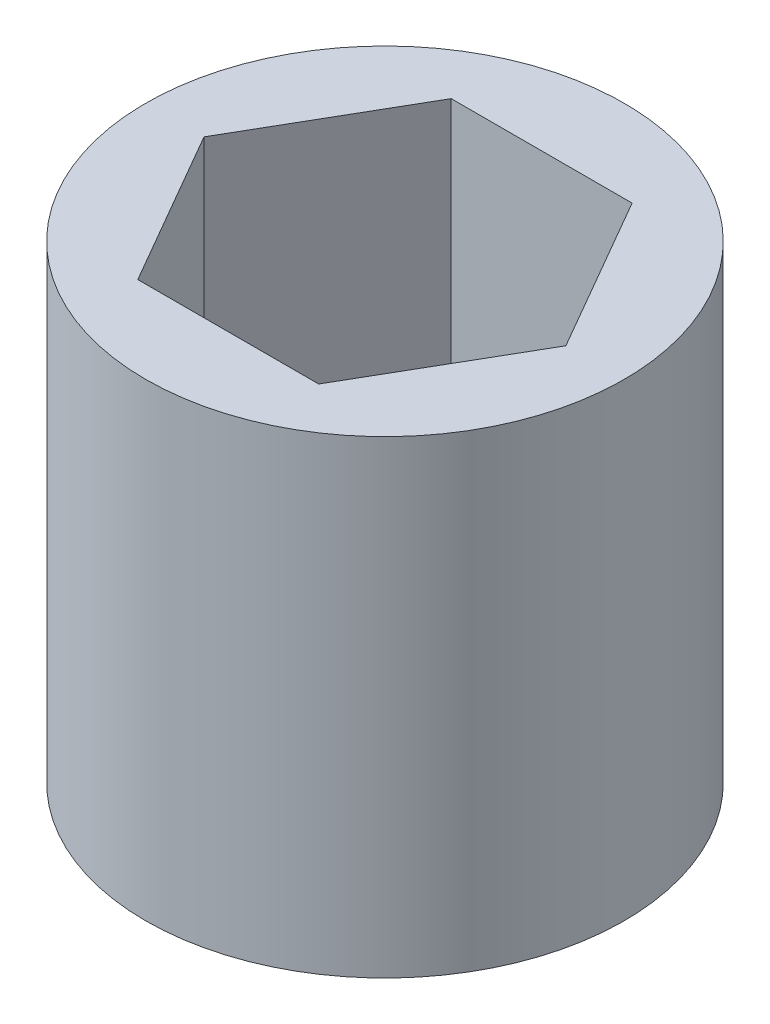
SolidWorks part; units mm, degrees
ref_plane "Front Plane" through (0, 0, 0) normal (0, 0, 1) x (1, 0, 0)
ref_plane "Top Plane" through (0, 0, 0) normal (0, 1, 0) x (1, 0, 0)
ref_plane "Right Plane" through (0, 0, 0) normal (1, 0, 0) x (0, 0, -1)
sketch "Sketch1" plane through (0, 0, 0) normal (0, 1, 0) x (1, 0, 0)
  line L0 (-2.8362, -4.9125) -> (2.8362, -4.9125)
  line L1 (2.8362, -4.9125) -> (5.6725, 0)
  line L2 (5.6725, 0) -> (2.8362, 4.9125)
  line L3 (2.8362, 4.9125) -> (-2.8362, 4.9125)
  line L4 (-2.8362, 4.9125) -> (-5.6725, 0)
  line L5 (-5.6725, 0) -> (-2.8362, -4.9125)
  circle A0 centre (0, 0) radius 7.5
  point P7 (0, 0)
  point P9 (0, 4.9125)
  dimension "D3" = 15
  dimension "D1" = 120
  dimension "D2" = 9.825
extrude "Boss-Extrude1" add sketch "Sketch1" along normal mid plane 14.7
ref_axis "Axis1" through (0, 0, 0) along (0, 1, 0)
